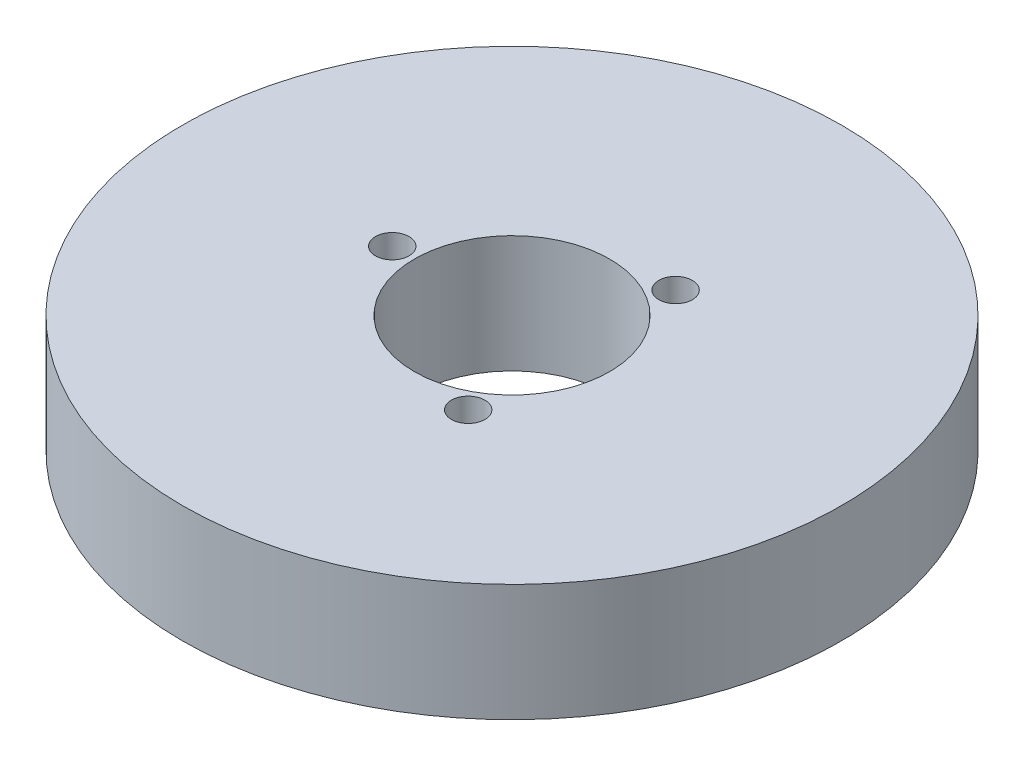
SolidWorks part; units mm, degrees
ref_plane "Front Plane" through (0, 0, 0) normal (0, 0, 1) x (1, 0, 0)
ref_plane "Top Plane" through (0, 0, 0) normal (0, 1, 0) x (1, 0, 0)
ref_plane "Right Plane" through (0, 0, 0) normal (1, 0, 0) x (0, 0, -1)
sketch "Sketch1" plane through (0, 0, 0) normal (0, 1, 0) x (1, 0, 0)
  circle A0 centre (0, 0) radius 67.5
  dimension "FLANGE_OD" = 135
extrude "Boss-Extrude1" add sketch "Sketch1" along normal blind 24
sketch "Sketch2" plane through (0, 0, 0) normal (0, 1, 0) x (1, 0, 0)
  circle A0 centre (0, 0) radius 20
  dimension "BORE_D" = 40
extrude "Cut-Extrude1" cut sketch "Sketch2" along normal through all
sketch "Sketch3" plane through (0, 24, 0) normal (0, 1, 0) x (1, 0, 0)
  circle A0 centre (0, 0) radius 24.5283 construction
  circle A1 centre (-24.5283, 0) radius 3.4348
  dimension "BOLT_D" = 6.8696
  dimension "BOLT_PCD" = 49.0566
extrude "Cut-Extrude2" cut sketch "Sketch3" against normal blind 18.9822
pattern_circular "CirPattern1" count 3 over 360 about axis through (0, 0, 0) along (0, 1, 0) of "Cut-Extrude2"
